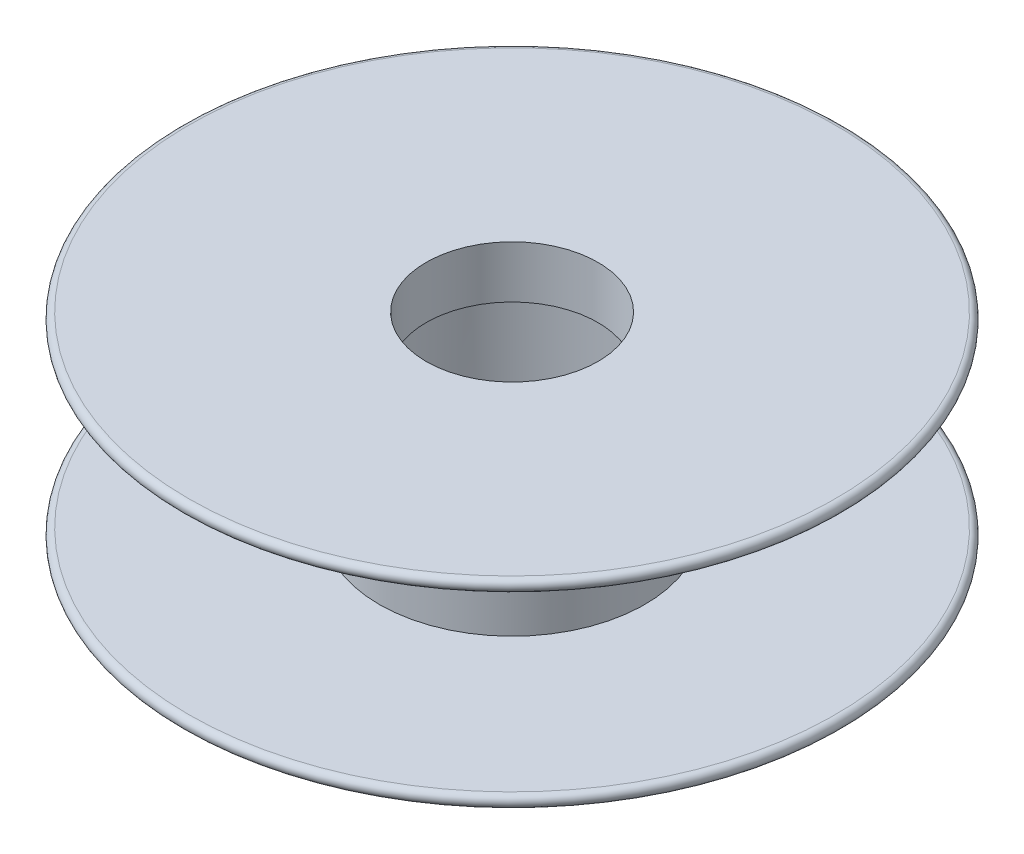
SolidWorks part; units mm, degrees
ref_plane "Front Plane" through (0, 0, 0) normal (0, 0, 1) x (1, 0, 0)
ref_plane "Top Plane" through (0, 0, 0) normal (0, 1, 0) x (1, 0, 0)
ref_plane "Right Plane" through (0, 0, 0) normal (1, 0, 0) x (0, 0, -1)
sketch "Sketch1" plane through (0, 0, 0) normal (0, 1, 0) x (1, 0, 0)
  circle A0 centre (0, 0) radius 99.25
  circle A1 centre (0, 0) radius 25.875
  dimension "D1" = 198.5
  dimension "D2" = 51.75
extrude "Boss-Extrude1" add sketch "Sketch1" along normal blind 3.7
fillet "Fillet1" 2 edges at (0, 3.7, 99.25) (0, 0, 99.25) type full round first side face at (0, 3.7, 99.25) second side face at (0, 0, 99.25) middle face at (0, 3.7, 99.25)
sketch "Sketch2" plane through (0, 3.7, 0) normal (0, 1, 0) x (1, 0, 0)
  circle A0 centre (0, 0) radius 40
  circle A1 centre (0, 0) radius 25.875 construction
  circle A2 centre (0, 0) radius 25.875
  dimension "D1" = 80
extrude "Boss-Extrude2" add sketch "Sketch2" along normal blind 12
ref_plane "Plane1" through (0, 30, 0) normal (0, 1, 0) x (1, 0, 0)
mirror "Mirror2" about plane through (0, 30, 0) normal (0, 1, 0) of bodies 102
sketch "Sketch3" plane through (0, 44.3, 0) normal (0, -1, 0) x (1, 0, 0)
  circle A0 centre (0, 0) radius 35
  circle A1 centre (0, 0) radius 40
  circle A2 centre (0, 0) radius 40
  dimension "D1" = 0
  dimension "D2" = 5
extrude "Boss-Extrude3" add sketch "Sketch3" along normal up to surface (28.6 mm away) up to face at (0, 15.7, 40)
